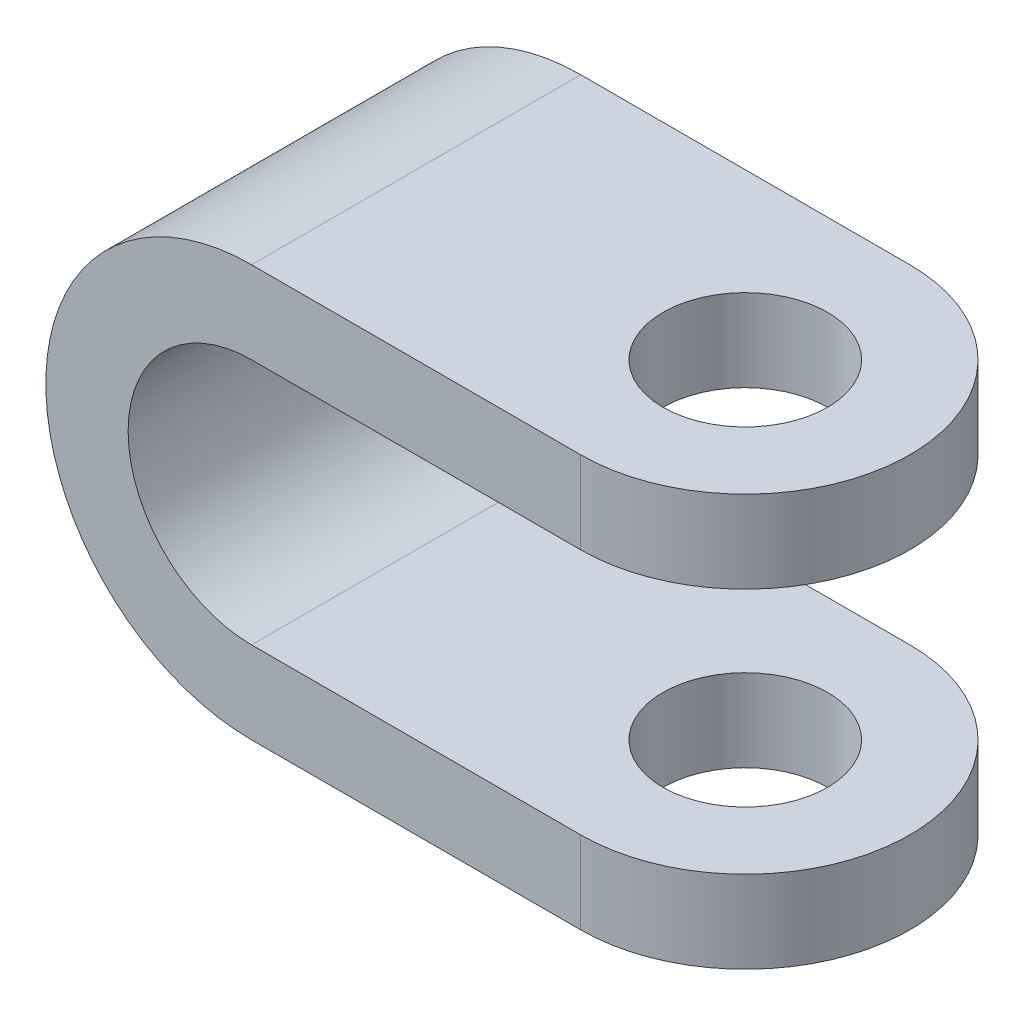
SolidWorks part; units mm, degrees
ref_plane "Front" through (0, 0, 0) normal (0, 0, 1) x (1, 0, 0)
ref_plane "Top" through (0, 0, 0) normal (0, 1, 0) x (1, 0, 0)
ref_plane "Right" through (0, 0, 0) normal (1, 0, 0) x (0, 0, -1)
sketch "Sketch1" plane through (0, 0, 0) normal (0, 0, 1) x (1, 0, 0)
  line L0 (0, -15) -> (-60, -15)
  line L1 (-60, -65) -> (0, -65)
  arc A0 (-60, -15) -> (-60, -65) centre (-60, -40) ccw
  dimension "D3" = 25
  dimension "D1" = 15
  dimension "D2" = 60
extrude "Extrude-Thin1" add sketch "Sketch1" along normal blind 90 thin thin type one direction reverse wall 10
sketch "Sketch2" plane through (0, 0, 0) normal (0, 1, 0) x (1, 0, 0)
  line L0 (-85, -25) -> (-85, -65)
  line L1 (-85, 0) -> (-85, -90) construction
  line L2 (-85, -65) -> (-20, -65)
  line L3 (-20, -25) -> (-85, -25)
  line L4 (0, -90) -> (0, 0) construction
  arc A0 (-20, -65) -> (-20, -25) centre (-20, -45) ccw
  circle A1 centre (-20, -45) radius 10
  dimension "D2" = 25
  dimension "D3" = 20
  dimension "D1" = 40
extrude "Boss-Extrude1" add sketch "Sketch2" against normal blind 90 separate body
combine bodies "组合1" operation type common bodies to combine 101 102
